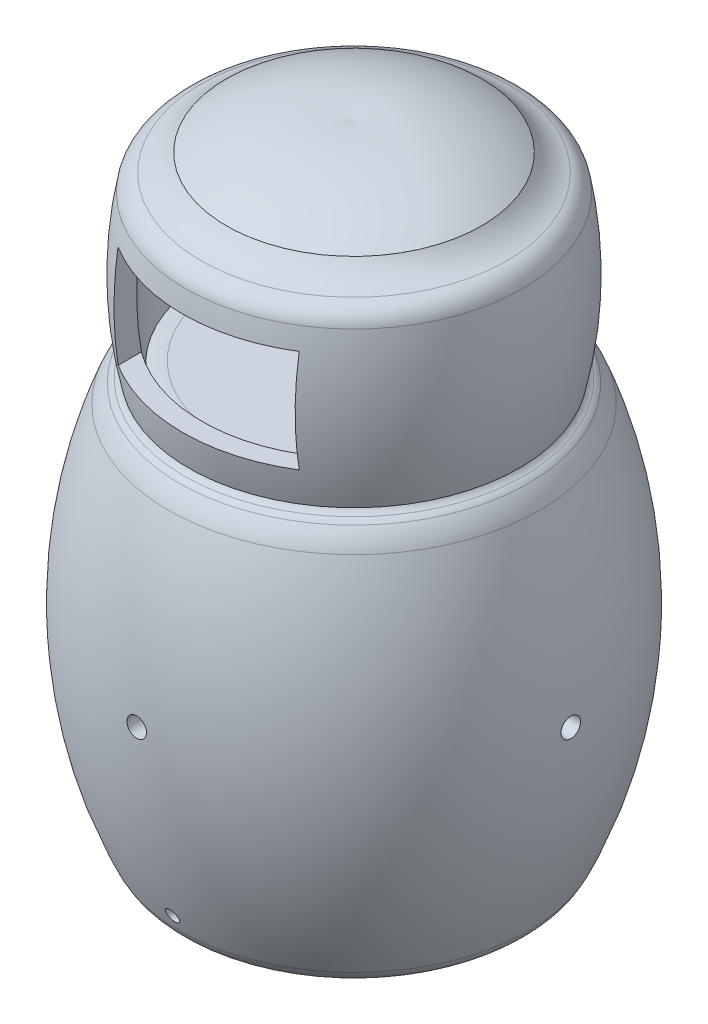
SolidWorks part; units mm, degrees
ref_plane "Front Plane" through (0, 0, 0) normal (0, 0, 1) x (1, 0, 0)
ref_plane "Top Plane" through (0, 0, 0) normal (0, 1, 0) x (1, 0, 0)
ref_plane "Right Plane" through (0, 0, 0) normal (1, 0, 0) x (0, 0, -1)
sketch "Sketch2" plane through (0, 0, 0) normal (0, 0, 1) x (1, 0, 0)
  line L0 (0, 300) -> (0, -290) construction
  line L1 (-142.8245, 0) -> (143.6743, 0) construction
  line L2 (-202.362, 110.7345) -> (365.1962, 110.7345) construction
  line L3 (0, -20) -> (-90, -20) construction
  line L4 (-90, -83.4454) -> (-90, 331.1943) construction
  line L8 (-20.6932, 220) -> (-90, 220)
  line L9 (-20.6932, 205) -> (-90, 205)
  line L10 (-90, 220) -> (-90, 205)
  line L11 (-4.9262, 0) -> (-19.2818, 0)
  line L12 (-19.2818, 0) -> (-19.2818, 12.4799)
  line L13 (-19.2818, 12.4799) -> (-12.1346, 13.1544)
  line L14 (-3.4461, 214.5466) -> (-3.4461, 304.5466) construction
  line L15 (-90, 330) -> (0, 330) construction
  line L16 (-88.8438, 320.0671) -> (-90, 320.0671)
  line L17 (-90, 320.0671) -> (-90, 330)
  arc A0 (1.5112, 6.9259) -> (7.2919, 200.8089) centre (-225.9175, 110.7345) ccw
  arc A2 (1.5112, 6.9259) -> (-4.9262, 0) centre (-12.1346, 13.1544) cw
  arc A10 (-12.1346, 13.1544) -> (-12.1346, 13.1544) centre (-12.1346, 13.1544) cw
  arc A11 (-12.1346, 13.1544) -> (-6.7007, 195.4045) centre (-225.9175, 110.7345) ccw
  arc A12 (-20.6932, 205) -> (-6.7007, 195.4045) centre (-20.6932, 190) cw
  arc A13 (-9.7505, 305.6891) -> (-23.0961, 314.8325) centre (-1.798, 331.6077) cw
  arc A14 (-23.0961, 314.8325) -> (-90, 330) centre (-78.0678, 227.4928) ccw
  arc A15 (-1.8255, 296.8392) -> (-3.4461, 214.5466) centre (-198.3178, 259.5466) cw
  arc A16 (-1.8255, 296.8392) -> (-9.7505, 305.6891) centre (-13.1238, 294.6949) ccw
  arc A17 (1.5294, 210.1533) -> (7.2919, 200.8089) centre (-20.6932, 190) cw
  arc A18 (-20.6932, 220) -> (-3.4461, 214.5466) centre (-20.6932, 190) cw
  arc A19 (-3.4461, 214.5466) -> (-1.0214, 212.1769) centre (2.1016, 217.7977) ccw
  arc A20 (-20.6932, 220) -> (7.2919, 200.8089) centre (-20.6932, 190) cw construction
  arc A21 (1.5294, 210.1533) -> (-1.0214, 212.1769) centre (-5.8781, 203.4355) ccw
  arc A22 (-11.6501, 294.9746) -> (-13.1897, 216.7966) centre (-198.3178, 259.5466) cw
  arc A23 (-11.6501, 294.9746) -> (-12.6838, 296.1289) centre (-13.1238, 294.6949) ccw
  arc A24 (-12.6838, 296.1289) -> (-29.7371, 307.1814) centre (-1.798, 331.6077) cw
  arc A25 (-29.7371, 307.1814) -> (-88.8438, 320.0671) centre (-78.0678, 227.4928) ccw
  point P11 (-86.4792, 156.5384)
  point P13 (-4.944, -0.0828)
  point P14 (0, 0)
  point P30 (-6.5748, 7.2962)
  point P31 (-86.4792, 156.5384)
  point P32 (-89.8547, -12.7145)
  point P50 (0, 211.7207)
  dimension "D3" = 250
  dimension "D6" = 15
  dimension "D7" = 15
  dimension "D1" = 30
  dimension "D4" = 220
  dimension "D10" = 200
  dimension "D11" = 11.5
  dimension "D12" = 10
  dimension "D2" = 90
  dimension "D5" = 20
  dimension "D8" = 110
  dimension "D9" = 90
  dimension "D13" = 10
revolve "Revolve1" add sketch "Sketch2" angle 360 about L4 region at (-16.999, 217.2727, 0)
sketch "Sketch3" plane through (0, 0, 0) normal (0, -1, 0) x (1, 0, 0)
  circle A0 centre (-90, 0) radius 77.5012
  circle A1 centre (-90, 0) radius 81
  dimension "D1" = 155.0025
  dimension "D2" = 162
extrude "Cut-Extrude1" cut sketch "Sketch3" against normal blind 20
revolve "Revolve2" add sketch "Sketch2<3>" angle 360 about L4 region at (-6.8568, 256.8724, 0)
sketch "Sketch2<3>" plane through (0, 0, 0) normal (0, 0, 1) x (1, 0, 0) same geometry as "Sketch2"
ref_plane "Plane1" through (0, 0, 91.7) normal (0, 0, 1) x (1, 0, 0)
sketch "Sketch4" plane through (0, 0, 91.7) normal (0, 0, 1) x (1, 0, 0)
  line L0 (-90, 296.8392) -> (-90, -16.2259) construction
  line L1 (-137.52, 286.2685) -> (-42.48, 286.2685)
  line L2 (-137.52, 286.2685) -> (-137.52, 232.4085)
  line L3 (-137.52, 232.4085) -> (-42.48, 232.4085)
  line L4 (-42.48, 286.2685) -> (-42.48, 232.4085)
  line L5 (-1.8255, 296.8392) -> (-178.1745, 296.8392) construction
  line L6 (-137.52, 232.4085) -> (-42.48, 286.2685) construction
  line L7 (-137.52, 286.2685) -> (-42.48, 232.4085) construction
  point P8 (-90, 259.3385)
  dimension "D1" = 53.86
  dimension "D2" = 95.04
extrude "Cut-Extrude2" cut sketch "Sketch4" against normal blind 30
sketch "Sketch5" plane through (0, 220, 0) normal (0, 1, 0) x (1, 0, 0)
  circle A0 centre (-90, 0) radius 20
  dimension "D1" = 40
extrude "Cut-Extrude3" cut sketch "Sketch5" against normal blind 20
sketch "Sketch6" plane through (0, 0, 91.7) normal (0, 0, 1) x (1, 0, 0)
  line L0 (-90, 0) -> (-90, 330) construction
  line L1 (-175.0738, 0) -> (-4.9262, 0) construction
  line L2 (-204.0825, 110.7345) -> (38.389, 110.7345) construction
  arc A0 (-187.2919, 200.8089) -> (-181.5112, 6.9259) centre (45.9175, 110.7345) ccw construction
  circle A1 centre (-90, 110.7345) radius 5.1
  dimension "D1" = 10.2
extrude "Cut-Extrude4" cut sketch "Sketch6" against normal blind 410 and the other way blind 30
sketch "Sketch7" plane through (0, 0, 0) normal (1, 0, 0) x (0, 0, -1)
  line L0 (0, 330) -> (0, 0) construction
  line L1 (-113.8915, 110.7345) -> (113.402, 110.7345) construction
  circle A0 centre (-0.2448, 110.7345) radius 5.1
  dimension "D1" = 10.2
extrude "Cut-Extrude5" cut sketch "Sketch7" against normal through all both and the other way through all
sketch "Sketch8" plane through (0, 0, 91.7) normal (0, 0, 1) x (1, 0, 0)
  line L0 (-90, 0) -> (-90, 330) construction
  line L1 (-175.0738, 0) -> (-4.9262, 0) construction
  circle A0 centre (-90, 15.6297) radius 3.55
  dimension "D1" = 7.1
extrude "Cut-Extrude6" cut sketch "Sketch8" against normal blind 12 and the other way through all
